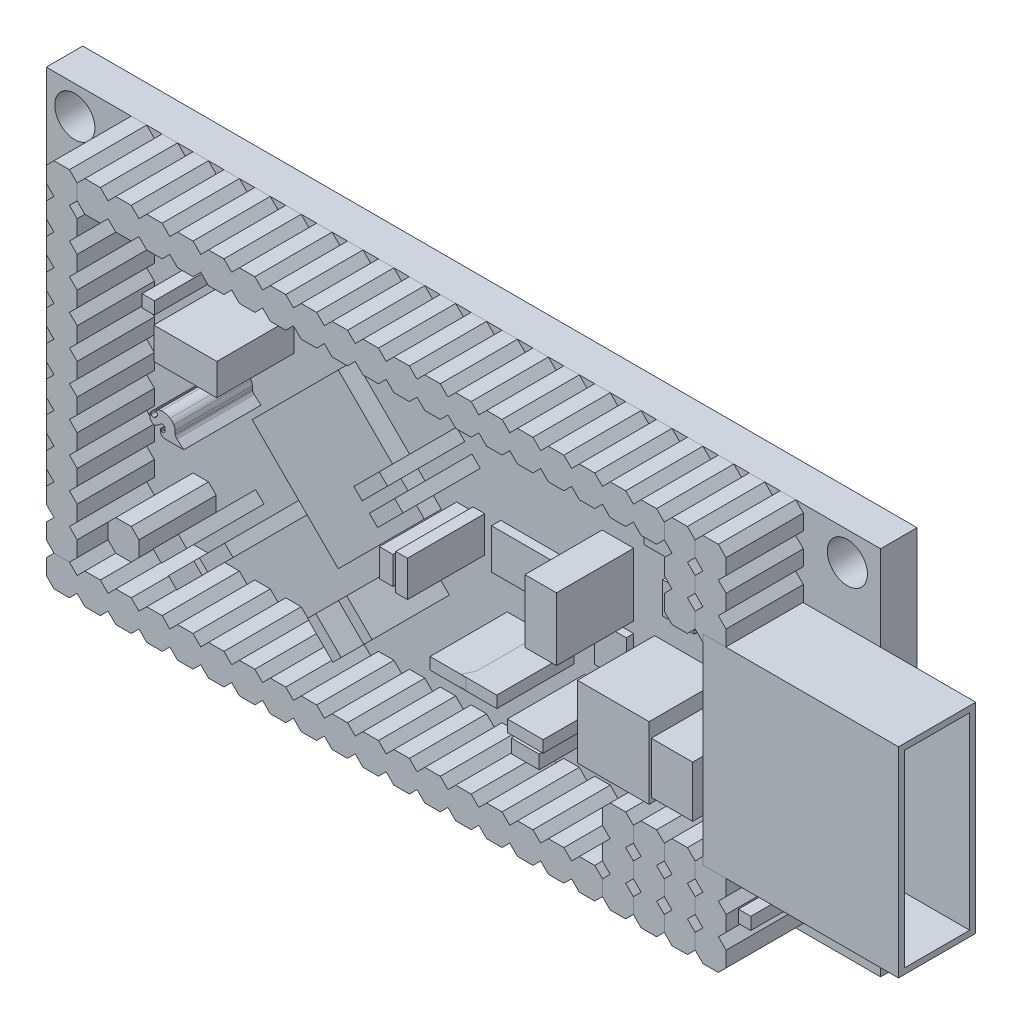
SolidWorks part; units mm, degrees
ref_plane "정면" through (0, 0, 0) normal (0, 0, 1) x (1, 0, 0)
ref_plane "윗면" through (0, 0, 0) normal (0, 1, 0) x (1, 0, 0)
ref_plane "우측면" through (0, 0, 0) normal (1, 0, 0) x (0, 0, -1)
sketch "스케치1" plane through (0, 0, 0) normal (0, 0, 1) x (1, 0, 0)
  line L0 (50.8, 81.28) -> (50.8, 50.8)
  line L1 (50.8, 50.8) -> (119.38, 50.8)
  line L2 (119.38, 50.8) -> (119.38, 81.28)
  line L3 (119.38, 81.28) -> (50.8, 81.28)
extrude "BOARD" add sketch "스케치1" along normal blind 3 separate body
ref_plane "평면1" through (0, 0, 3) normal (0, 0, 1) x (1, 0, 0)
sketch "스케치2" plane through (0, 0, 3) normal (0, 0, 1) x (1, 0, 0)
  line L0 (81.8495, 62.343) -> (83.933, 60.2595)
  line L1 (83.933, 60.2595) -> (83.2505, 59.577)
  line L2 (83.2505, 59.577) -> (81.167, 61.6605)
  line L3 (81.167, 61.6605) -> (81.8495, 62.343)
extrude "0402-CAP-1" add sketch "스케치2" along normal blind 6.35 separate body
sketch "스케치3" plane through (0, 0, 3) normal (0, 0, 1) x (1, 0, 0)
  line L0 (82.437, 70.4195) -> (84.5205, 72.503)
  line L1 (84.5205, 72.503) -> (85.203, 71.8205)
  line L2 (85.203, 71.8205) -> (83.1195, 69.737)
  line L3 (83.1195, 69.737) -> (82.437, 70.4195)
extrude "0402-CAP-2" add sketch "스케치3" along normal blind 6.35 separate body
sketch "스케치4" plane through (0, 0, 3) normal (0, 0, 1) x (1, 0, 0)
  line L0 (79.3095, 59.803) -> (81.393, 57.7195)
  line L1 (81.393, 57.7195) -> (80.7105, 57.037)
  line L2 (80.7105, 57.037) -> (78.627, 59.1205)
  line L3 (78.627, 59.1205) -> (79.3095, 59.803)
extrude "0402-CAP-3" add sketch "스케치4" along normal blind 6.35 separate body
sketch "스케치5" plane through (0, 0, 3) normal (0, 0, 1) x (1, 0, 0)
  line L0 (72.503, 60.3905) -> (70.4195, 58.307)
  line L1 (70.4195, 58.307) -> (69.737, 58.9895)
  line L2 (69.737, 58.9895) -> (71.8205, 61.073)
  line L3 (71.8205, 61.073) -> (72.503, 60.3905)
extrude "0402-CAP-4" add sketch "스케치5" along normal blind 6.35 separate body
sketch "스케치6" plane through (0, 0, 3) normal (0, 0, 1) x (1, 0, 0)
  line L0 (83.707, 69.1495) -> (85.7905, 71.233)
  line L1 (85.7905, 71.233) -> (86.473, 70.5505)
  line L2 (86.473, 70.5505) -> (84.3895, 68.467)
  line L3 (84.3895, 68.467) -> (83.707, 69.1495)
extrude "0402-CAP-5" add sketch "스케치6" along normal blind 6.35 separate body
sketch "스케치7" plane through (0, 0, 3) normal (0, 0, 1) x (1, 0, 0)
  line L0 (107.2896, 69.9262) -> (109.8804, 69.9262)
  line L1 (109.8804, 69.9262) -> (109.8804, 66.7258)
  line L2 (109.8804, 66.7258) -> (107.2896, 66.7258)
  line L3 (107.2896, 66.7258) -> (107.2896, 69.9262)
extrude "1210-1" add sketch "스케치7" along normal blind 0.6096 separate body
sketch "스케치8" plane through (0, 0, 3) normal (0, 0, 1) x (1, 0, 0)
  line L0 (65.9892, 71.0946) -> (71.1708, 71.0946)
  line L1 (71.1708, 71.0946) -> (71.1708, 73.6854)
  line L2 (71.1708, 73.6854) -> (65.9892, 73.6854)
  line L3 (65.9892, 73.6854) -> (65.9892, 71.0946)
extrude "EIA3216-1" add sketch "스케치8" along normal blind 6.35 separate body
sketch "스케치9" plane through (0, 0, 3) normal (0, 0, 1) x (1, 0, 0)
  line L0 (99.0854, 65.9892) -> (99.0854, 71.1708)
  line L1 (99.0854, 71.1708) -> (96.4946, 71.1708)
  line L2 (96.4946, 71.1708) -> (96.4946, 65.9892)
  line L3 (96.4946, 65.9892) -> (99.0854, 65.9892)
extrude "EIA3216-2" add sketch "스케치9" along normal blind 6.35 separate body
sketch "스케치10" plane through (0, 0, 3) normal (0, 0, 1) x (1, 0, 0)
  line L0 (99.0854, 61.8998) -> (96.4946, 61.8998)
  line L1 (96.4946, 61.8998) -> (96.4946, 65.1002)
  line L2 (96.4946, 65.1002) -> (99.0854, 65.1002)
  line L3 (99.0854, 65.1002) -> (99.0854, 61.8998)
extrude "1210-2" add sketch "스케치10" along normal blind 0.6096 separate body
sketch "스케치11" plane through (0, 0, 3) normal (0, 0, 1) x (1, 0, 0)
  line L0 (100.5586, 72.4662) -> (103.1494, 72.4662)
  line L1 (103.1494, 72.4662) -> (103.1494, 73.8378)
  line L2 (103.1494, 73.8378) -> (100.5586, 73.8378)
  line L3 (100.5586, 73.8378) -> (100.5586, 72.4662)
extrude "0805-1" add sketch "스케치11" along normal blind 0.6096 separate body
sketch "스케치12" plane through (0, 0, 3) normal (0, 0, 1) x (1, 0, 0)
  line L0 (88.1634, 67.691) -> (94.7166, 67.691)
  line L1 (94.7166, 67.691) -> (94.7166, 64.389)
  line L2 (94.7166, 64.389) -> (88.1634, 64.389)
  line L3 (88.1634, 64.389) -> (88.1634, 67.691)
extrude "SOT223-1" add sketch "스케치12" along normal blind 0.762 separate body
sketch "스케치13" plane through (0, 0, 3) normal (0, 0, 1) x (1, 0, 0)
  line L0 (87.63, 80.645) -> (88.265, 81.28)
  line L1 (88.265, 81.28) -> (89.535, 81.28)
  line L2 (89.535, 81.28) -> (90.17, 80.645)
  line L3 (90.17, 80.645) -> (90.805, 81.28)
  line L4 (90.805, 81.28) -> (92.075, 81.28)
  line L5 (92.075, 81.28) -> (92.71, 80.645)
  line L6 (92.71, 80.645) -> (93.345, 81.28)
  line L7 (93.345, 81.28) -> (94.615, 81.28)
  line L8 (94.615, 81.28) -> (95.25, 80.645)
  line L9 (95.25, 80.645) -> (95.885, 81.28)
  line L10 (95.885, 81.28) -> (97.155, 81.28)
  line L11 (97.155, 81.28) -> (97.79, 80.645)
  line L12 (97.79, 80.645) -> (98.425, 81.28)
  line L13 (98.425, 81.28) -> (99.695, 81.28)
  line L14 (99.695, 81.28) -> (100.33, 80.645)
  line L15 (100.33, 80.645) -> (100.965, 81.28)
  line L16 (100.965, 81.28) -> (102.235, 81.28)
  line L17 (102.235, 81.28) -> (102.87, 80.645)
  line L18 (102.87, 80.645) -> (103.505, 81.28)
  line L19 (103.505, 81.28) -> (104.775, 81.28)
  line L20 (104.775, 81.28) -> (105.41, 80.645)
  line L21 (105.41, 80.645) -> (106.045, 81.28)
  line L22 (106.045, 81.28) -> (107.315, 81.28)
  line L23 (107.315, 81.28) -> (107.95, 80.645)
  line L24 (107.95, 80.645) -> (107.95, 79.375)
  line L25 (107.95, 79.375) -> (107.315, 78.74)
  line L26 (107.315, 78.74) -> (106.045, 78.74)
  line L27 (106.045, 78.74) -> (105.41, 79.375)
  line L28 (105.41, 79.375) -> (104.775, 78.74)
  line L29 (104.775, 78.74) -> (103.505, 78.74)
  line L30 (103.505, 78.74) -> (102.87, 79.375)
  line L31 (102.87, 79.375) -> (102.235, 78.74)
  line L32 (102.235, 78.74) -> (100.965, 78.74)
  line L33 (100.965, 78.74) -> (100.33, 79.375)
  line L34 (100.33, 79.375) -> (99.695, 78.74)
  line L35 (99.695, 78.74) -> (98.425, 78.74)
  line L36 (98.425, 78.74) -> (97.79, 79.375)
  line L37 (97.79, 79.375) -> (97.155, 78.74)
  line L38 (97.155, 78.74) -> (95.885, 78.74)
  line L39 (95.885, 78.74) -> (95.25, 79.375)
  line L40 (95.25, 79.375) -> (94.615, 78.74)
  line L41 (94.615, 78.74) -> (93.345, 78.74)
  line L42 (93.345, 78.74) -> (92.71, 79.375)
  line L43 (92.71, 79.375) -> (92.075, 78.74)
  line L44 (92.075, 78.74) -> (90.805, 78.74)
  line L45 (90.805, 78.74) -> (90.17, 79.375)
  line L46 (90.17, 79.375) -> (89.535, 78.74)
  line L47 (89.535, 78.74) -> (88.265, 78.74)
  line L48 (88.265, 78.74) -> (87.63, 79.375)
  line L49 (87.63, 79.375) -> (86.995, 78.74)
  line L50 (86.995, 78.74) -> (85.725, 78.74)
  line L51 (85.725, 78.74) -> (85.09, 79.375)
  line L52 (85.09, 79.375) -> (84.455, 78.74)
  line L53 (84.455, 78.74) -> (83.185, 78.74)
  line L54 (83.185, 78.74) -> (82.55, 79.375)
  line L55 (82.55, 79.375) -> (81.915, 78.74)
  line L56 (81.915, 78.74) -> (80.645, 78.74)
  line L57 (80.645, 78.74) -> (80.01, 79.375)
  line L58 (80.01, 79.375) -> (79.375, 78.74)
  line L59 (79.375, 78.74) -> (78.105, 78.74)
  line L60 (78.105, 78.74) -> (77.47, 79.375)
  line L61 (77.47, 79.375) -> (76.835, 78.74)
  line L62 (76.835, 78.74) -> (75.565, 78.74)
  line L63 (75.565, 78.74) -> (74.93, 79.375)
  line L64 (74.93, 79.375) -> (74.295, 78.74)
  line L65 (74.295, 78.74) -> (73.025, 78.74)
  line L66 (73.025, 78.74) -> (72.39, 79.375)
  line L67 (72.39, 79.375) -> (71.755, 78.74)
  line L68 (71.755, 78.74) -> (70.485, 78.74)
  line L69 (70.485, 78.74) -> (69.85, 79.375)
  line L70 (69.85, 79.375) -> (69.215, 78.74)
  line L71 (69.215, 78.74) -> (67.945, 78.74)
  line L72 (67.945, 78.74) -> (67.31, 79.375)
  line L73 (67.31, 79.375) -> (66.675, 78.74)
  line L74 (66.675, 78.74) -> (65.405, 78.74)
  line L75 (65.405, 78.74) -> (64.77, 79.375)
  line L76 (64.77, 79.375) -> (64.135, 78.74)
  line L77 (64.135, 78.74) -> (62.865, 78.74)
  line L78 (62.865, 78.74) -> (62.23, 79.375)
  line L79 (62.23, 79.375) -> (61.595, 78.74)
  line L80 (61.595, 78.74) -> (60.325, 78.74)
  line L81 (60.325, 78.74) -> (59.69, 79.375)
  line L82 (59.69, 79.375) -> (59.69, 80.645)
  line L83 (59.69, 80.645) -> (60.325, 81.28)
  line L84 (60.325, 81.28) -> (61.595, 81.28)
  line L85 (61.595, 81.28) -> (62.23, 80.645)
  line L86 (62.23, 80.645) -> (62.865, 81.28)
  line L87 (62.865, 81.28) -> (64.135, 81.28)
  line L88 (64.135, 81.28) -> (64.77, 80.645)
  line L89 (64.77, 80.645) -> (65.405, 81.28)
  line L90 (65.405, 81.28) -> (66.675, 81.28)
  line L91 (66.675, 81.28) -> (67.31, 80.645)
  line L92 (67.31, 80.645) -> (67.945, 81.28)
  line L93 (67.945, 81.28) -> (69.215, 81.28)
  line L94 (69.215, 81.28) -> (69.85, 80.645)
  line L95 (69.85, 80.645) -> (70.485, 81.28)
  line L96 (70.485, 81.28) -> (71.755, 81.28)
  line L97 (71.755, 81.28) -> (72.39, 80.645)
  line L98 (72.39, 80.645) -> (73.025, 81.28)
  line L99 (73.025, 81.28) -> (74.295, 81.28)
  line L100 (74.295, 81.28) -> (74.93, 80.645)
  line L101 (74.93, 80.645) -> (75.565, 81.28)
  line L102 (75.565, 81.28) -> (76.835, 81.28)
  line L103 (76.835, 81.28) -> (77.47, 80.645)
  line L104 (77.47, 80.645) -> (78.105, 81.28)
  line L105 (78.105, 81.28) -> (79.375, 81.28)
  line L106 (79.375, 81.28) -> (80.01, 80.645)
  line L107 (80.01, 80.645) -> (80.645, 81.28)
  line L108 (80.645, 81.28) -> (81.915, 81.28)
  line L109 (81.915, 81.28) -> (82.55, 80.645)
  line L110 (82.55, 80.645) -> (83.185, 81.28)
  line L111 (83.185, 81.28) -> (84.455, 81.28)
  line L112 (84.455, 81.28) -> (85.09, 80.645)
  line L113 (85.09, 80.645) -> (85.725, 81.28)
  line L114 (85.725, 81.28) -> (86.995, 81.28)
  line L115 (86.995, 81.28) -> (87.63, 80.645)
extrude "1X19-1" add sketch "스케치13" along normal blind 6.35 separate body
sketch "스케치14" plane through (0, 0, 3) normal (0, 0, 1) x (1, 0, 0)
  line L0 (107.95, 79.375) -> (107.95, 80.645)
  line L1 (107.95, 80.645) -> (108.585, 81.28)
  line L2 (108.585, 81.28) -> (109.855, 81.28)
  line L3 (109.855, 81.28) -> (110.49, 80.645)
  line L4 (110.49, 80.645) -> (110.49, 79.375)
  line L5 (110.49, 79.375) -> (109.855, 78.74)
  line L6 (109.855, 78.74) -> (110.49, 78.105)
  line L7 (110.49, 78.105) -> (110.49, 76.835)
  line L8 (110.49, 76.835) -> (109.855, 76.2)
  line L9 (109.855, 76.2) -> (110.49, 75.565)
  line L10 (110.49, 75.565) -> (110.49, 74.295)
  line L11 (110.49, 74.295) -> (109.855, 73.66)
  line L12 (109.855, 73.66) -> (108.585, 73.66)
  line L13 (108.585, 73.66) -> (107.95, 74.295)
  line L14 (107.95, 74.295) -> (107.95, 75.565)
  line L15 (107.95, 75.565) -> (108.585, 76.2)
  line L16 (108.585, 76.2) -> (107.95, 76.835)
  line L17 (107.95, 76.835) -> (107.95, 78.105)
  line L18 (107.95, 78.105) -> (108.585, 78.74)
  line L19 (108.585, 78.74) -> (107.95, 79.375)
extrude "1X03-1" add sketch "스케치14" along normal blind 6.35 separate body
sketch "스케치15" plane through (0, 0, 3) normal (0, 0, 1) x (1, 0, 0)
  line L0 (113.03, 75.565) -> (113.03, 74.295)
  line L1 (113.03, 74.295) -> (112.395, 73.66)
  line L2 (112.395, 73.66) -> (111.125, 73.66)
  line L3 (111.125, 73.66) -> (110.49, 74.295)
  line L4 (110.49, 74.295) -> (110.49, 75.565)
  line L5 (110.49, 75.565) -> (111.125, 76.2)
  line L6 (111.125, 76.2) -> (110.49, 76.835)
  line L7 (110.49, 76.835) -> (110.49, 78.105)
  line L8 (110.49, 78.105) -> (111.125, 78.74)
  line L9 (111.125, 78.74) -> (110.49, 79.375)
  line L10 (110.49, 79.375) -> (110.49, 80.645)
  line L11 (110.49, 80.645) -> (111.125, 81.28)
  line L12 (111.125, 81.28) -> (112.395, 81.28)
  line L13 (112.395, 81.28) -> (113.03, 80.645)
  line L14 (113.03, 80.645) -> (113.03, 79.375)
  line L15 (113.03, 79.375) -> (112.395, 78.74)
  line L16 (112.395, 78.74) -> (113.03, 78.105)
  line L17 (113.03, 78.105) -> (113.03, 76.835)
  line L18 (113.03, 76.835) -> (112.395, 76.2)
  line L19 (112.395, 76.2) -> (113.03, 75.565)
extrude "1X03-2" add sketch "스케치15" along normal blind 6.35 separate body
sketch "스케치16" plane through (0, 0, 3) normal (0, 0, 1) x (1, 0, 0)
  line L0 (110.49, 56.515) -> (110.49, 57.785)
  line L1 (110.49, 57.785) -> (111.125, 58.42)
  line L2 (111.125, 58.42) -> (112.395, 58.42)
  line L3 (112.395, 58.42) -> (113.03, 57.785)
  line L4 (113.03, 57.785) -> (113.03, 56.515)
  line L5 (113.03, 56.515) -> (112.395, 55.88)
  line L6 (112.395, 55.88) -> (113.03, 55.245)
  line L7 (113.03, 55.245) -> (113.03, 53.975)
  line L8 (113.03, 53.975) -> (112.395, 53.34)
  line L9 (112.395, 53.34) -> (113.03, 52.705)
  line L10 (113.03, 52.705) -> (113.03, 51.435)
  line L11 (113.03, 51.435) -> (112.395, 50.8)
  line L12 (112.395, 50.8) -> (111.125, 50.8)
  line L13 (111.125, 50.8) -> (110.49, 51.435)
  line L14 (110.49, 51.435) -> (110.49, 52.705)
  line L15 (110.49, 52.705) -> (111.125, 53.34)
  line L16 (111.125, 53.34) -> (110.49, 53.975)
  line L17 (110.49, 53.975) -> (110.49, 55.245)
  line L18 (110.49, 55.245) -> (111.125, 55.88)
  line L19 (111.125, 55.88) -> (110.49, 56.515)
extrude "1X03-3" add sketch "스케치16" along normal blind 6.35 separate body
sketch "스케치17" plane through (0, 0, 3) normal (0, 0, 1) x (1, 0, 0)
  line L0 (105.41, 56.515) -> (105.41, 57.785)
  line L1 (105.41, 57.785) -> (106.045, 58.42)
  line L2 (106.045, 58.42) -> (107.315, 58.42)
  line L3 (107.315, 58.42) -> (107.95, 57.785)
  line L4 (107.95, 57.785) -> (107.95, 56.515)
  line L5 (107.95, 56.515) -> (107.315, 55.88)
  line L6 (107.315, 55.88) -> (107.95, 55.245)
  line L7 (107.95, 55.245) -> (107.95, 53.975)
  line L8 (107.95, 53.975) -> (107.315, 53.34)
  line L9 (107.315, 53.34) -> (107.95, 52.705)
  line L10 (107.95, 52.705) -> (107.95, 51.435)
  line L11 (107.95, 51.435) -> (107.315, 50.8)
  line L12 (107.315, 50.8) -> (106.045, 50.8)
  line L13 (106.045, 50.8) -> (105.41, 51.435)
  line L14 (105.41, 51.435) -> (105.41, 52.705)
  line L15 (105.41, 52.705) -> (106.045, 53.34)
  line L16 (106.045, 53.34) -> (105.41, 53.975)
  line L17 (105.41, 53.975) -> (105.41, 55.245)
  line L18 (105.41, 55.245) -> (106.045, 55.88)
  line L19 (106.045, 55.88) -> (105.41, 56.515)
extrude "1X03-4" add sketch "스케치17" along normal blind 6.35 separate body
sketch "스케치18" plane through (0, 0, 3) normal (0, 0, 1) x (1, 0, 0)
  line L0 (107.95, 56.515) -> (107.95, 57.785)
  line L1 (107.95, 57.785) -> (108.585, 58.42)
  line L2 (108.585, 58.42) -> (109.855, 58.42)
  line L3 (109.855, 58.42) -> (110.49, 57.785)
  line L4 (110.49, 57.785) -> (110.49, 56.515)
  line L5 (110.49, 56.515) -> (109.855, 55.88)
  line L6 (109.855, 55.88) -> (110.49, 55.245)
  line L7 (110.49, 55.245) -> (110.49, 53.975)
  line L8 (110.49, 53.975) -> (109.855, 53.34)
  line L9 (109.855, 53.34) -> (110.49, 52.705)
  line L10 (110.49, 52.705) -> (110.49, 51.435)
  line L11 (110.49, 51.435) -> (109.855, 50.8)
  line L12 (109.855, 50.8) -> (108.585, 50.8)
  line L13 (108.585, 50.8) -> (107.95, 51.435)
  line L14 (107.95, 51.435) -> (107.95, 52.705)
  line L15 (107.95, 52.705) -> (108.585, 53.34)
  line L16 (108.585, 53.34) -> (107.95, 53.975)
  line L17 (107.95, 53.975) -> (107.95, 55.245)
  line L18 (107.95, 55.245) -> (108.585, 55.88)
  line L19 (108.585, 55.88) -> (107.95, 56.515)
extrude "1X03-5" add sketch "스케치18" along normal blind 6.35 separate body
sketch "스케치19" plane through (0, 0, 3) normal (0, 0, 1) x (1, 0, 0)
  line L0 (114.046, 55.118) -> (115.062, 55.118)
  line L1 (115.062, 55.118) -> (115.062, 56.134)
  line L2 (115.062, 56.134) -> (114.046, 56.134)
  line L3 (114.046, 56.134) -> (114.046, 55.118)
extrude "FIDUCIAL-1X2-1" add sketch "스케치19" along normal blind 6.35 separate body
sketch "스케치21" plane through (0, 0, 3) normal (0, 0, 1) x (1, 0, 0)
  line L0 (82.55, 52.705) -> (83.185, 53.34)
  line L1 (83.185, 53.34) -> (84.455, 53.34)
  line L2 (84.455, 53.34) -> (85.09, 52.705)
  line L3 (85.09, 52.705) -> (85.725, 53.34)
  line L4 (85.725, 53.34) -> (86.995, 53.34)
  line L5 (86.995, 53.34) -> (87.63, 52.705)
  line L6 (87.63, 52.705) -> (88.265, 53.34)
  line L7 (88.265, 53.34) -> (89.535, 53.34)
  line L8 (89.535, 53.34) -> (90.17, 52.705)
  line L9 (90.17, 52.705) -> (90.805, 53.34)
  line L10 (90.805, 53.34) -> (92.075, 53.34)
  line L11 (92.075, 53.34) -> (92.71, 52.705)
  line L12 (92.71, 52.705) -> (93.345, 53.34)
  line L13 (93.345, 53.34) -> (94.615, 53.34)
  line L14 (94.615, 53.34) -> (95.25, 52.705)
  line L15 (95.25, 52.705) -> (95.885, 53.34)
  line L16 (95.885, 53.34) -> (97.155, 53.34)
  line L17 (97.155, 53.34) -> (97.79, 52.705)
  line L18 (97.79, 52.705) -> (98.425, 53.34)
  line L19 (98.425, 53.34) -> (99.695, 53.34)
  line L20 (99.695, 53.34) -> (100.33, 52.705)
  line L21 (100.33, 52.705) -> (100.965, 53.34)
  line L22 (100.965, 53.34) -> (102.235, 53.34)
  line L23 (102.235, 53.34) -> (102.87, 52.705)
  line L24 (102.87, 52.705) -> (102.87, 51.435)
  line L25 (102.87, 51.435) -> (102.235, 50.8)
  line L26 (102.235, 50.8) -> (100.965, 50.8)
  line L27 (100.965, 50.8) -> (100.33, 51.435)
  line L28 (100.33, 51.435) -> (99.695, 50.8)
  line L29 (99.695, 50.8) -> (98.425, 50.8)
  line L30 (98.425, 50.8) -> (97.79, 51.435)
  line L31 (97.79, 51.435) -> (97.155, 50.8)
  line L32 (97.155, 50.8) -> (95.885, 50.8)
  line L33 (95.885, 50.8) -> (95.25, 51.435)
  line L34 (95.25, 51.435) -> (94.615, 50.8)
  line L35 (94.615, 50.8) -> (93.345, 50.8)
  line L36 (93.345, 50.8) -> (92.71, 51.435)
  line L37 (92.71, 51.435) -> (92.075, 50.8)
  line L38 (92.075, 50.8) -> (90.805, 50.8)
  line L39 (90.805, 50.8) -> (90.17, 51.435)
  line L40 (90.17, 51.435) -> (89.535, 50.8)
  line L41 (89.535, 50.8) -> (88.265, 50.8)
  line L42 (88.265, 50.8) -> (87.63, 51.435)
  line L43 (87.63, 51.435) -> (86.995, 50.8)
  line L44 (86.995, 50.8) -> (85.725, 50.8)
  line L45 (85.725, 50.8) -> (85.09, 51.435)
  line L46 (85.09, 51.435) -> (84.455, 50.8)
  line L47 (84.455, 50.8) -> (83.185, 50.8)
  line L48 (83.185, 50.8) -> (82.55, 51.435)
  line L49 (82.55, 51.435) -> (81.915, 50.8)
  line L50 (81.915, 50.8) -> (80.645, 50.8)
  line L51 (80.645, 50.8) -> (80.01, 51.435)
  line L52 (80.01, 51.435) -> (79.375, 50.8)
  line L53 (79.375, 50.8) -> (78.105, 50.8)
  line L54 (78.105, 50.8) -> (77.47, 51.435)
  line L55 (77.47, 51.435) -> (76.835, 50.8)
  line L56 (76.835, 50.8) -> (75.565, 50.8)
  line L57 (75.565, 50.8) -> (74.93, 51.435)
  line L58 (74.93, 51.435) -> (74.295, 50.8)
  line L59 (74.295, 50.8) -> (73.025, 50.8)
  line L60 (73.025, 50.8) -> (72.39, 51.435)
  line L61 (72.39, 51.435) -> (71.755, 50.8)
  line L62 (71.755, 50.8) -> (70.485, 50.8)
  line L63 (70.485, 50.8) -> (69.85, 51.435)
  line L64 (69.85, 51.435) -> (69.215, 50.8)
  line L65 (69.215, 50.8) -> (67.945, 50.8)
  line L66 (67.945, 50.8) -> (67.31, 51.435)
  line L67 (67.31, 51.435) -> (66.675, 50.8)
  line L68 (66.675, 50.8) -> (65.405, 50.8)
  line L69 (65.405, 50.8) -> (64.77, 51.435)
  line L70 (64.77, 51.435) -> (64.135, 50.8)
  line L71 (64.135, 50.8) -> (62.865, 50.8)
  line L72 (62.865, 50.8) -> (62.23, 51.435)
  line L73 (62.23, 51.435) -> (61.595, 50.8)
  line L74 (61.595, 50.8) -> (60.325, 50.8)
  line L75 (60.325, 50.8) -> (59.69, 51.435)
  line L76 (59.69, 51.435) -> (59.055, 50.8)
  line L77 (59.055, 50.8) -> (57.785, 50.8)
  line L78 (57.785, 50.8) -> (57.15, 51.435)
  line L79 (57.15, 51.435) -> (57.15, 52.705)
  line L80 (57.15, 52.705) -> (57.785, 53.34)
  line L81 (57.785, 53.34) -> (59.055, 53.34)
  line L82 (59.055, 53.34) -> (59.69, 52.705)
  line L83 (59.69, 52.705) -> (60.325, 53.34)
  line L84 (60.325, 53.34) -> (61.595, 53.34)
  line L85 (61.595, 53.34) -> (62.23, 52.705)
  line L86 (62.23, 52.705) -> (62.865, 53.34)
  line L87 (62.865, 53.34) -> (64.135, 53.34)
  line L88 (64.135, 53.34) -> (64.77, 52.705)
  line L89 (64.77, 52.705) -> (65.405, 53.34)
  line L90 (65.405, 53.34) -> (66.675, 53.34)
  line L91 (66.675, 53.34) -> (67.31, 52.705)
  line L92 (67.31, 52.705) -> (67.945, 53.34)
  line L93 (67.945, 53.34) -> (69.215, 53.34)
  line L94 (69.215, 53.34) -> (69.85, 52.705)
  line L95 (69.85, 52.705) -> (70.485, 53.34)
  line L96 (70.485, 53.34) -> (71.755, 53.34)
  line L97 (71.755, 53.34) -> (72.39, 52.705)
  line L98 (72.39, 52.705) -> (73.025, 53.34)
  line L99 (73.025, 53.34) -> (74.295, 53.34)
  line L100 (74.295, 53.34) -> (74.93, 52.705)
  line L101 (74.93, 52.705) -> (75.565, 53.34)
  line L102 (75.565, 53.34) -> (76.835, 53.34)
  line L103 (76.835, 53.34) -> (77.47, 52.705)
  line L104 (77.47, 52.705) -> (78.105, 53.34)
  line L105 (78.105, 53.34) -> (79.375, 53.34)
  line L106 (79.375, 53.34) -> (80.01, 52.705)
  line L107 (80.01, 52.705) -> (80.645, 53.34)
  line L108 (80.645, 53.34) -> (81.915, 53.34)
  line L109 (81.915, 53.34) -> (82.55, 52.705)
extrude "1X18-1" add sketch "스케치21" along normal blind 6.35 separate body
sketch "스케치26" plane through (0, 0, 3) normal (0, 0, 1) x (1, 0, 0)
  line L0 (59.69, 78.105) -> (59.055, 78.74)
  line L1 (59.055, 78.74) -> (59.69, 79.375)
  line L2 (59.69, 79.375) -> (59.69, 80.645)
  line L3 (59.69, 80.645) -> (59.055, 81.28)
  line L4 (59.055, 81.28) -> (57.785, 81.28)
  line L5 (57.785, 81.28) -> (57.15, 80.645)
  line L6 (57.15, 80.645) -> (57.15, 79.375)
  line L7 (57.15, 79.375) -> (57.785, 78.74)
  line L8 (57.785, 78.74) -> (57.15, 78.105)
  line L9 (57.15, 78.105) -> (57.15, 76.835)
  line L10 (57.15, 76.835) -> (57.785, 76.2)
  line L11 (57.785, 76.2) -> (57.15, 75.565)
  line L12 (57.15, 75.565) -> (57.15, 74.295)
  line L13 (57.15, 74.295) -> (57.785, 73.66)
  line L14 (57.785, 73.66) -> (57.15, 73.025)
  line L15 (57.15, 73.025) -> (57.15, 71.755)
  line L16 (57.15, 71.755) -> (57.785, 71.12)
  line L17 (57.785, 71.12) -> (57.15, 70.485)
  line L18 (57.15, 70.485) -> (57.15, 69.215)
  line L19 (57.15, 69.215) -> (57.785, 68.58)
  line L20 (57.785, 68.58) -> (57.15, 67.945)
  line L21 (57.15, 67.945) -> (57.15, 66.675)
  line L22 (57.15, 66.675) -> (57.785, 66.04)
  line L23 (57.785, 66.04) -> (57.15, 65.405)
  line L24 (57.15, 65.405) -> (57.15, 64.135)
  line L25 (57.15, 64.135) -> (57.785, 63.5)
  line L26 (57.785, 63.5) -> (57.15, 62.865)
  line L27 (57.15, 62.865) -> (57.15, 61.595)
  line L28 (57.15, 61.595) -> (57.785, 60.96)
  line L29 (57.785, 60.96) -> (57.15, 60.325)
  line L30 (57.15, 60.325) -> (57.15, 59.055)
  line L31 (57.15, 59.055) -> (57.785, 58.42)
  line L32 (57.785, 58.42) -> (57.15, 57.785)
  line L33 (57.15, 57.785) -> (57.15, 56.515)
  line L34 (57.15, 56.515) -> (57.785, 55.88)
  line L35 (57.785, 55.88) -> (57.15, 55.245)
  line L36 (57.15, 55.245) -> (57.15, 53.975)
  line L37 (57.15, 53.975) -> (57.785, 53.34)
  line L38 (57.785, 53.34) -> (59.055, 53.34)
  line L39 (59.055, 53.34) -> (59.69, 53.975)
  line L40 (59.69, 53.975) -> (59.69, 55.245)
  line L41 (59.69, 55.245) -> (59.055, 55.88)
  line L42 (59.055, 55.88) -> (59.69, 56.515)
  line L43 (59.69, 56.515) -> (59.69, 57.785)
  line L44 (59.69, 57.785) -> (59.055, 58.42)
  line L45 (59.055, 58.42) -> (59.69, 59.055)
  line L46 (59.69, 59.055) -> (59.69, 60.325)
  line L47 (59.69, 60.325) -> (59.055, 60.96)
  line L48 (59.055, 60.96) -> (59.69, 61.595)
  line L49 (59.69, 61.595) -> (59.69, 62.865)
  line L50 (59.69, 62.865) -> (59.055, 63.5)
  line L51 (59.055, 63.5) -> (59.69, 64.135)
  line L52 (59.69, 64.135) -> (59.69, 65.405)
  line L53 (59.69, 65.405) -> (59.055, 66.04)
  line L54 (59.055, 66.04) -> (59.69, 66.675)
  line L55 (59.69, 66.675) -> (59.69, 67.945)
  line L56 (59.69, 67.945) -> (59.055, 68.58)
  line L57 (59.055, 68.58) -> (59.69, 69.215)
  line L58 (59.69, 69.215) -> (59.69, 70.485)
  line L59 (59.69, 70.485) -> (59.055, 71.12)
  line L60 (59.055, 71.12) -> (59.69, 71.755)
  line L61 (59.69, 71.755) -> (59.69, 73.025)
  line L62 (59.69, 73.025) -> (59.055, 73.66)
  line L63 (59.055, 73.66) -> (59.69, 74.295)
  line L64 (59.69, 74.295) -> (59.69, 75.565)
  line L65 (59.69, 75.565) -> (59.055, 76.2)
  line L66 (59.055, 76.2) -> (59.69, 76.835)
  line L67 (59.69, 76.835) -> (59.69, 78.105)
extrude "1X11-1" add sketch "스케치26" along normal blind 6.35 separate body
sketch "스케치27" plane through (0, 0, 3) normal (0, 0, 1) x (1, 0, 0)
  line L0 (64.77, 56.515) -> (64.77, 57.785)
  line L1 (64.77, 57.785) -> (64.135, 58.42)
  line L2 (64.135, 58.42) -> (62.865, 58.42)
  line L3 (62.865, 58.42) -> (62.23, 57.785)
  line L4 (62.23, 57.785) -> (62.23, 56.515)
  line L5 (62.23, 56.515) -> (62.865, 55.88)
  line L6 (62.865, 55.88) -> (64.135, 55.88)
  line L7 (64.135, 55.88) -> (64.77, 56.515)
extrude "1X01-1" add sketch "스케치27" along normal blind 6.35 separate body
sketch "스케치28" plane through (0, 0, 3) normal (0, 0, 1) x (1, 0, 0)
  line L0 (66.548, 66.5988) -> (66.548, 66.548)
  line L1 (66.929, 66.04) -> (68.453, 66.04)
  line L2 (68.453, 66.04) -> (67.8942, 66.5226)
  line L3 (67.7418, 66.802) -> (67.7418, 67.0306)
  line L4 (66.1162, 67.5894) -> (66.1924, 67.5894)
  line L5 (66.2686, 67.3354) -> (66.1924, 67.2338)
  arc A0 (66.548, 66.548) -> (66.548, 66.3448) centre (67.2278, 66.4464) ccw
  arc A1 (66.548, 66.3448) -> (66.7004, 66.1162) centre (66.8935, 66.41) ccw
  arc A2 (66.7004, 66.1162) -> (66.929, 66.04) centre (66.9355, 66.4406) ccw
  arc A3 (67.8942, 66.5226) -> (67.7672, 66.7258) centre (68.3301, 66.9363) cw
  arc A4 (67.7672, 66.7258) -> (67.7418, 66.802) centre (67.9822, 66.8398) cw
  arc A5 (67.7418, 67.0306) -> (67.6402, 67.4116) centre (67.0041, 67.0379) ccw
  arc A6 (67.6402, 67.4116) -> (67.3354, 67.7164) centre (66.7708, 66.847) ccw
  arc A7 (67.3354, 67.7164) -> (66.5988, 67.8942) centre (66.7293, 66.8202) ccw
  arc A8 (66.5988, 67.8942) -> (66.3194, 67.7926) centre (66.6882, 67.2133) ccw
  arc A9 (66.3194, 67.7926) -> (66.1162, 67.5894) centre (66.6958, 67.213) ccw
  arc A10 (66.1924, 67.5894) -> (66.2178, 67.5894) centre (66.2051, 67.542) cw
  arc A11 (66.2178, 67.5894) -> (66.294, 67.5132) centre (66.1273, 67.4227) cw
  arc A12 (66.294, 67.5132) -> (66.294, 67.4878) centre (66.1621, 67.5005) cw
  arc A13 (66.294, 67.4878) -> (66.2686, 67.3354) centre (66.1141, 67.4395) cw
  arc A14 (66.1924, 67.2338) -> (66.1162, 67.1576) centre (65.8994, 67.4506) cw
  arc A15 (66.1162, 67.1576) -> (66.0146, 67.1068) centre (65.905, 67.4529) cw
  arc A16 (66.0146, 67.1068) -> (65.9638, 67.1068) centre (65.9892, 67.2126) cw
  arc A17 (65.9638, 67.1068) -> (65.786, 67.2338) centre (65.9849, 67.3243) cw
  arc A18 (65.786, 67.2338) -> (65.7606, 67.3354) centre (66.094, 67.3648) cw
  arc A19 (65.7606, 67.3354) -> (65.7606, 67.4116) centre (67.2156, 67.3735) cw
  arc A20 (65.7606, 67.4116) -> (65.7098, 67.31) centre (65.9389, 67.2589) ccw
  arc A21 (65.7098, 67.31) -> (65.6844, 67.2846) centre (65.5856, 67.4088) cw
  arc A22 (65.6844, 67.2846) -> (65.6844, 67.2592) centre (65.8163, 67.2719) ccw
  arc A23 (65.6844, 67.2592) -> (65.659, 67.0814) centre (66.2665, 67.0853) ccw
  arc A24 (65.659, 67.0814) -> (65.7098, 66.8274) centre (66.1131, 67.0401) ccw
  arc A25 (65.7098, 66.8274) -> (65.8368, 66.675) centre (66.3521, 67.2335) ccw
  arc A26 (65.8368, 66.675) -> (66.1924, 66.6496) centre (66.0321, 66.907) ccw
  arc A27 (66.1924, 66.6496) -> (66.5226, 66.9036) centre (65.5557, 67.819) ccw
  arc A28 (66.5226, 66.9036) -> (66.8782, 66.8782) centre (66.6905, 66.752) cw
  arc A29 (66.8782, 66.8782) -> (66.929, 66.7004) centre (66.547, 66.6874) cw
  arc A30 (66.929, 66.7004) -> (66.8782, 66.4972) centre (66.6389, 66.665) cw
  arc A31 (66.8782, 66.4972) -> (66.802, 66.421) centre (66.7072, 66.592) cw
  arc A32 (66.802, 66.421) -> (66.6496, 66.421) centre (66.7258, 66.6487) cw
  arc A33 (66.6496, 66.421) -> (66.6242, 66.4464) centre (66.6772, 66.474) cw
  arc A34 (66.6242, 66.4464) -> (66.5734, 66.548) centre (60.7777, 63.5866) ccw
  arc A35 (66.5734, 66.548) -> (66.548, 66.5988) centre (66.6152, 66.6006) cw
extrude "SFE-LOGO-FLAME-1" add sketch "스케치28" along normal blind 6.35 separate body
sketch "스케치29" plane through (0, 0, 3) normal (0, 0, 1) x (1, 0, 0)
  line L0 (105.41, 52.705) -> (105.41, 51.435)
  line L1 (105.41, 51.435) -> (104.775, 50.8)
  line L2 (104.775, 50.8) -> (103.505, 50.8)
  line L3 (103.505, 50.8) -> (102.87, 51.435)
  line L4 (102.87, 51.435) -> (102.87, 52.705)
  line L5 (102.87, 52.705) -> (103.505, 53.34)
  line L6 (103.505, 53.34) -> (102.87, 53.975)
  line L7 (102.87, 53.975) -> (102.87, 55.245)
  line L8 (102.87, 55.245) -> (103.505, 55.88)
  line L9 (103.505, 55.88) -> (102.87, 56.515)
  line L10 (102.87, 56.515) -> (102.87, 57.785)
  line L11 (102.87, 57.785) -> (103.505, 58.42)
  line L12 (103.505, 58.42) -> (104.775, 58.42)
  line L13 (104.775, 58.42) -> (105.41, 57.785)
  line L14 (105.41, 57.785) -> (105.41, 56.515)
  line L15 (105.41, 56.515) -> (104.775, 55.88)
  line L16 (104.775, 55.88) -> (105.41, 55.245)
  line L17 (105.41, 55.245) -> (105.41, 53.975)
  line L18 (105.41, 53.975) -> (104.775, 53.34)
  line L19 (104.775, 53.34) -> (105.41, 52.705)
extrude "1X03-6" add sketch "스케치29" along normal blind 6.35 separate body
sketch "스케치30" plane through (0, 0, 3) normal (0, 0, 1) x (1, 0, 0)
  line L0 (65.024, 74.422) -> (66.04, 74.422)
  line L1 (66.04, 74.422) -> (66.04, 75.438)
  line L2 (66.04, 75.438) -> (65.024, 75.438)
  line L3 (65.024, 75.438) -> (65.024, 74.422)
extrude "FIDUCIAL-1X2-2" add sketch "스케치30" along normal blind 6.35 separate body
sketch "스케치32" plane through (0, 0, 3) normal (0, 0, 1) x (1, 0, 0)
  line L0 (106.7054, 59.9186) -> (106.7054, 65.8114)
  line L1 (106.7054, 65.8114) -> (100.8126, 65.8114)
  line L2 (100.8126, 65.8114) -> (100.8126, 59.9186)
  line L3 (100.8126, 59.9186) -> (106.7054, 59.9186)
extrude "SRU5028-1" add sketch "스케치32" along normal blind 6.35 separate body
sketch "스케치33" plane through (0, 0, 3) normal (0, 0, 1) x (1, 0, 0)
  line L0 (84.5312, 64.897) -> (85.6488, 64.897)
  line L1 (85.6488, 64.897) -> (85.6488, 67.183)
  line L2 (85.6488, 67.183) -> (84.5312, 67.183)
  line L3 (84.5312, 67.183) -> (84.5312, 64.897)
extrude "LED-0603-1" add sketch "스케치33" along normal blind 6.35 separate body
sketch "스케치34" plane through (0, 0, 3) normal (0, 0, 1) x (1, 0, 0)
  line L0 (97.663, 57.8612) -> (97.663, 58.9788)
  line L1 (97.663, 58.9788) -> (95.377, 58.9788)
  line L2 (95.377, 58.9788) -> (95.377, 57.8612)
  line L3 (95.377, 57.8612) -> (97.663, 57.8612)
extrude "LED-0603-2" add sketch "스케치34" along normal blind 6.35 separate body
sketch "스케치35" plane through (0, 0, 3) normal (0, 0, 1) x (1, 0, 0)
  line L0 (67.197, 56.4495) -> (69.2805, 58.533)
  line L1 (69.2805, 58.533) -> (69.963, 57.8505)
  line L2 (69.963, 57.8505) -> (67.8795, 55.767)
  line L3 (67.8795, 55.767) -> (67.197, 56.4495)
extrude "0402-RES-1" add sketch "스케치35" along normal blind 6.35 separate body
sketch "스케치36" plane through (0, 0, 3) normal (0, 0, 1) x (1, 0, 0)
  line L0 (110.2868, 64.7192) -> (106.8832, 64.7192)
  line L1 (106.8832, 64.7192) -> (106.8832, 60.5028)
  line L2 (106.8832, 60.5028) -> (110.2868, 60.5028)
  line L3 (110.2868, 60.5028) -> (110.2868, 64.7192)
extrude "TRIMPOT-3MM-1" add sketch "스케치36" along normal blind 6.35 separate body
sketch "스케치37" plane through (0, 0, 3) normal (0, 0, 1) x (1, 0, 0)
  line L0 (88.6968, 61.4426) -> (91.6432, 61.4426)
  line L1 (91.6432, 61.4426) -> (91.6432, 60.4774)
  line L2 (91.6432, 60.4774) -> (88.6968, 60.4774)
  line L3 (88.6968, 60.4774) -> (88.6968, 61.4426)
extrude "0402-RES-2" add sketch "스케치37" along normal blind 6.35 separate body
sketch "스케치38" plane through (0, 0, 3) normal (0, 0, 1) x (1, 0, 0)
  line L0 (94.1832, 60.4774) -> (91.2368, 60.4774)
  line L1 (91.2368, 60.4774) -> (91.2368, 61.4426)
  line L2 (91.2368, 61.4426) -> (94.1832, 61.4426)
  line L3 (94.1832, 61.4426) -> (94.1832, 60.4774)
extrude "0402-RES-3" add sketch "스케치38" along normal blind 6.35 separate body
sketch "스케치39" plane through (0, 0, 3) normal (0, 0, 1) x (1, 0, 0)
  line L0 (85.8774, 64.5668) -> (85.8774, 67.5132)
  line L1 (85.8774, 67.5132) -> (86.8426, 67.5132)
  line L2 (86.8426, 67.5132) -> (86.8426, 64.5668)
  line L3 (86.8426, 64.5668) -> (85.8774, 64.5668)
extrude "0402-RES-4" add sketch "스케치39" along normal blind 6.35 separate body
sketch "스케치40" plane through (0, 0, 3) normal (0, 0, 1) x (1, 0, 0)
  line L0 (68.693, 59.1205) -> (66.6095, 57.037)
  line L1 (66.6095, 57.037) -> (65.927, 57.7195)
  line L2 (65.927, 57.7195) -> (68.0105, 59.803)
  line L3 (68.0105, 59.803) -> (68.693, 59.1205)
extrude "0402-RES-5" add sketch "스케치40" along normal blind 6.35 separate body
sketch "스케치41" plane through (0, 0, 3) normal (0, 0, 1) x (1, 0, 0)
  line L0 (97.9932, 59.2074) -> (95.0468, 59.2074)
  line L1 (95.0468, 59.2074) -> (95.0468, 60.1726)
  line L2 (95.0468, 60.1726) -> (97.9932, 60.1726)
  line L3 (97.9932, 60.1726) -> (97.9932, 59.2074)
extrude "0402-RES-6" add sketch "스케치41" along normal blind 6.35 separate body
sketch "스케치43" plane through (0, 0, 3) normal (0, 0, 1) x (1, 0, 0)
  line L0 (76.2, 73.1164) -> (83.2764, 66.04)
  line L1 (83.2764, 66.04) -> (76.2, 58.9636)
  line L2 (76.2, 58.9636) -> (69.1236, 66.04)
  line L3 (69.1236, 66.04) -> (76.2, 73.1164)
extrude "PIC24FXXX_TQFP64-1" add sketch "스케치43" along normal blind 1.397 separate body
sketch "스케치44" plane through (0, 0, 3) normal (0, 0, 1) x (1, 0, 0)
  line L0 (105.0544, 71.12) -> (102.4636, 71.12)
  line L1 (102.4636, 71.12) -> (102.4636, 68.5292)
  line L2 (102.4636, 68.5292) -> (105.0544, 68.5292)
  line L3 (105.0544, 68.5292) -> (105.0544, 71.12)
extrude "QFN16-4X4-1" add sketch "스케치44" along normal blind 0.9906 separate body
sketch "스케치45" plane through (0, 0, 3) normal (0, 0, 1) x (1, 0, 0)
  line L0 (127.2032, 74.2696) -> (111.125, 74.2696)
  line L1 (111.125, 74.2696) -> (111.125, 57.8104)
  line L2 (111.125, 57.8104) -> (127.2032, 57.8104)
  line L3 (127.2032, 57.8104) -> (127.2032, 74.2696)
extrude "USB-A-S-NOSILK-FEMALE-1" add sketch "스케치45" along normal blind 6.35 separate body
sketch "스케치47" plane through (127.2032, 0, 0) normal (1, 0, 0) x (0, 0, -1)
  line L0 (-9.35, 57.8104) -> (-9.35, 74.2696) construction
  line L1 (-8.85, 73.7696) -> (-3.5, 73.7696)
  line L2 (-8.85, 73.7696) -> (-8.85, 58.285)
  line L3 (-8.85, 58.285) -> (-3.5, 58.285)
  line L4 (-3.5, 73.7696) -> (-3.5, 58.285)
  line L5 (-9.35, 74.2696) -> (-3, 74.2696) construction
  line L6 (-3, 50.8) -> (-3, 81.28) construction
  line L7 (-9.35, 57.785) -> (-3, 57.785) construction
  dimension "D1" = 0.5
  dimension "D2" = 0.5
  dimension "D3" = 0.5
  dimension "D4" = 0.5
extrude "컷-돌출1" cut sketch "스케치47" against normal offset from surface (14.0782 mm away) 2 up to face at (111.125, 66.04, 6.175)
sketch "스케치50" plane through (0, 0, 3) normal (0, 0, 1) x (1, 0, 0)
  line L0 (119.38, 81.28) -> (50.8, 81.28) construction
  line L1 (50.8, 81.28) -> (50.8, 50.8) construction
  circle A0 centre (53.15, 78.93) radius 1.65
  dimension "D1" = 2.35
  dimension "D2" = 2.35
extrude "컷-돌출2" cut sketch "스케치50" against normal through all
pattern_linear "선형 패턴1" count 2 spacing 63.5 along (1, 0, 0) count 2 spacing 25.4 along (0, -1, 0) of "컷-돌출2"
